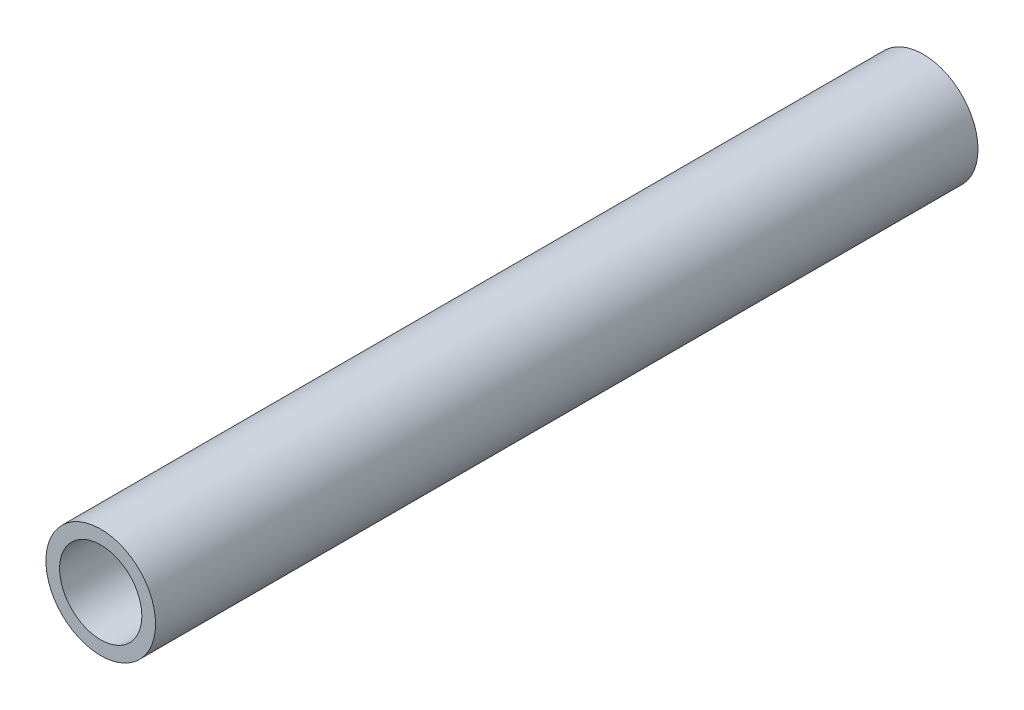
SolidWorks part; units mm, degrees
material "Lega 1060"
ref_plane "Piano frontale" through (0, 0, 0) normal (0, 0, 1) x (1, 0, 0)
ref_plane "Piano superiore" through (0, 0, 0) normal (0, 1, 0) x (1, 0, 0)
ref_plane "Piano destro" through (0, 0, 0) normal (1, 0, 0) x (0, 0, -1)
sketch "Schizzo1" plane through (0, 0, 0) normal (0, 0, 1) x (1, 0, 0)
  circle A0 centre (0, 0) radius 80
  circle A1 centre (0, 0) radius 60
  dimension "D1" = 160
  dimension "D2" = 120
extrude "Estrusione-Estrusione1" add sketch "Schizzo1" along normal blind 1200
